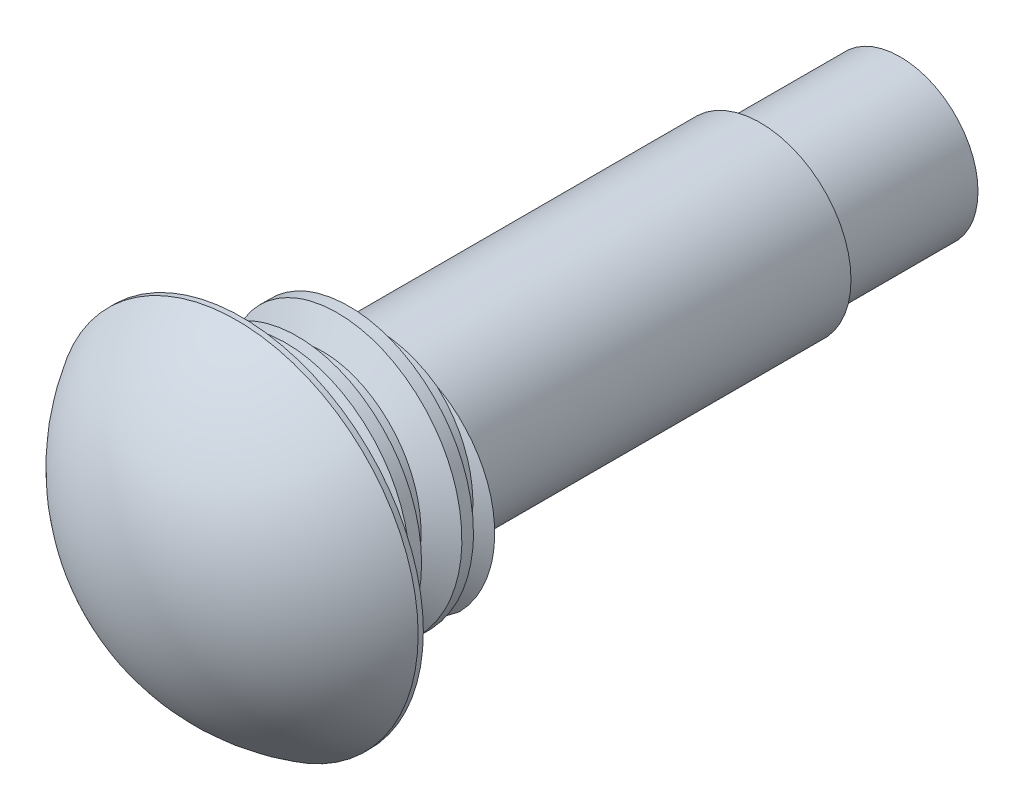
SolidWorks part; units mm, degrees
ref_plane "Front Plane" through (0, 0, 0) normal (0, 0, 1) x (1, 0, 0)
ref_plane "Top Plane" through (0, 0, 0) normal (0, 1, 0) x (1, 0, 0)
ref_plane "Right Plane" through (0, 0, 0) normal (1, 0, 0) x (0, 0, -1)
sketch "Sketch2" plane through (0, 0, 0) normal (0, 0, 1) x (1, 0, 0)
  circle A0 centre (0, 0) radius 3.175
curve "Helix/Spiral1" pitch 1.27 height 3.302 radius 3.175 left hand yes centre (0, 0, 0) axis (0, 0, 1) start towards (0, 1, 0)
sketch "Sketch3" plane through (0, 0, 0) normal (0, 0, 1) x (1, 0, 0)
  circle A0 centre (0, 0) radius 3.175
extrude "Boss-Extrude1" add sketch "Sketch3" along normal blind 3.302 contours A0
sketch "Sketch5" plane through (0, 0, 0) normal (1, 0, 0) x (0, 0, -1)
  line L0 (0.127, 2.54) -> (0.4936, 3.175)
  line L1 (0.4936, 3.175) -> (-0.4936, 3.175)
  line L2 (-0.4936, 3.175) -> (-0.127, 2.54)
  line L3 (-0.127, 2.54) -> (0.127, 2.54)
  line L4 (0, 3.175) -> (0, 2.54) construction
  dimension "D1" = 0.635
  dimension "D2" = 0.254
  dimension "D3" = 60
sweep "Cut-Sweep1" cut profiles "Sketch5" path "Helix/Spiral1" align with end faces yes
sketch "Sketch8" plane through (0, 0, 0) normal (0, 0, 1) x (1, 0, 0)
  circle A0 centre (0, 0) radius 2.2225
extrude "Boss-Extrude3" add sketch "Sketch8" against normal blind 9.398
sketch "Sketch10" plane through (0, 0, -9.398) normal (0, 0, -1) x (-1, 0, 0)
  circle A0 centre (0, 0) radius 1.905
extrude "Boss-Extrude5" add sketch "Sketch10" along normal blind 3.429
sketch "Sketch11" plane through (0, 0, 3.302) normal (0, 0, 1) x (1, 0, 0)
  circle A0 centre (0, 0) radius 4.445
extrude "Boss-Extrude6" add sketch "Sketch11" along normal blind 0.127
dome "Dome1" faces to dome 1 distance 2.54 reverse direction no elliptical dome no face at (4.445, 0, 3.429) parameters "D1"=2.54
